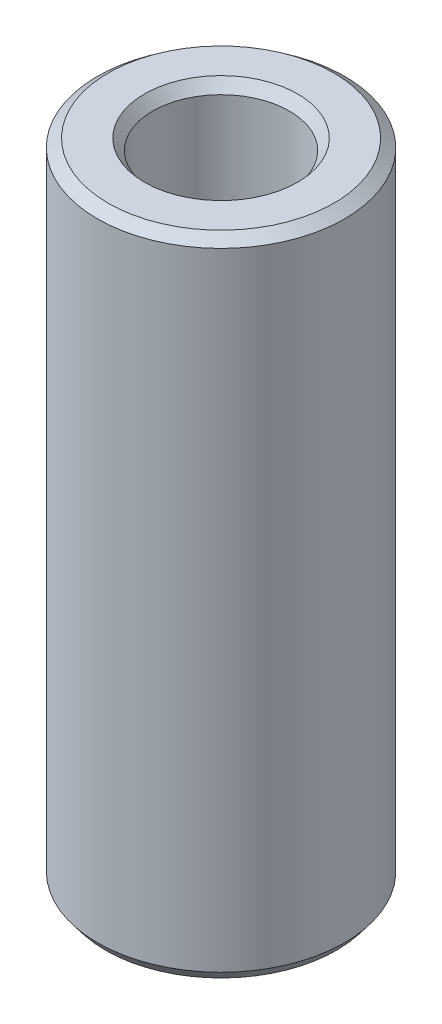
SolidWorks part; units mm, degrees
ref_plane "Front Plane" through (0, 0, 0) normal (0, 0, 1) x (1, 0, 0)
ref_plane "Top Plane" through (0, 0, 0) normal (0, 1, 0) x (1, 0, 0)
ref_plane "Right Plane" through (0, 0, 0) normal (1, 0, 0) x (0, 0, -1)
sketch "Sketch1" plane through (0, 0, 0) normal (0, 1, 0) x (1, 0, 0)
  circle A0 centre (0, 0) radius 57.5
  dimension "SLEEVE_OD" = 115
extrude "Boss-Extrude1" add sketch "Sketch1" along normal blind 300.5277
sketch "Sketch2" plane through (0, 0, 0) normal (0, 1, 0) x (1, 0, 0)
  circle A0 centre (0, 0) radius 31.8232
  dimension "BORE_D" = 63.6463
extrude "Cut-Extrude1" cut sketch "Sketch2" along normal through all
chamfer "Chamfer1" distance 3.8092 angle 52.66 4 edges at (0, 300.5277, 31.8232) (0, 0, 31.8232) (0, 0, 57.5) (0, 300.5277, 57.5) first distance on face at (0, 300.5277, 31.8232) first distance on face at (0, 0, 31.8232) first distance on face at (0, 300.5277, 57.5)
